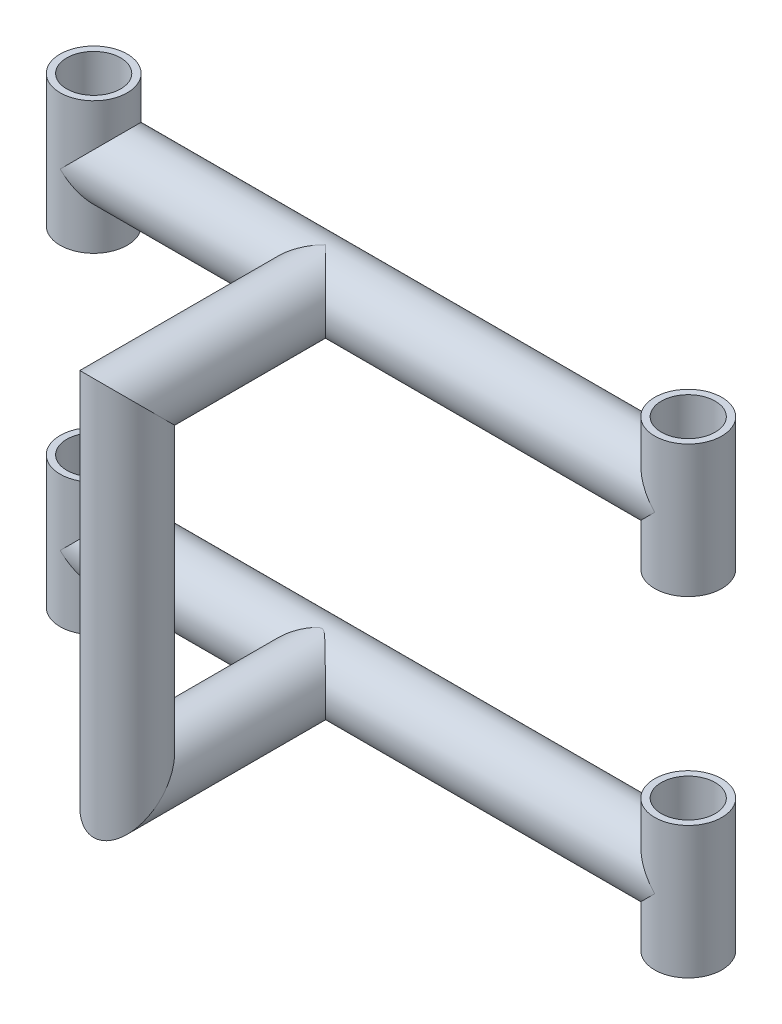
SolidWorks part; units mm, degrees
ref_plane "Alzado" through (0, 0, 0) normal (0, 0, 1) x (1, 0, 0)
ref_plane "Planta" through (0, 0, 0) normal (0, 1, 0) x (1, 0, 0)
ref_plane "Vista lateral" through (0, 0, 0) normal (1, 0, 0) x (0, 0, -1)
sketch "Croquis1" plane through (0, 0, 0) normal (0, 1, 0) x (1, 0, 0)
  circle A0 centre (0, 0) radius 25.4
  circle A1 centre (0, 0) radius 20.4
  dimension "D1" = 50.8
  dimension "D2" = 5
extrude "Saliente-Extruir1" add sketch "Croquis1" along normal blind 100
ref_plane "Plano3" through (0, 0, 0) normal (1, 0, 0) x (0, 0, -1)
sketch "Croquis7" plane through (0, 0, 0) normal (1, 0, 0) x (0, 0, -1)
  line L0 (-25.4, 100) -> (-25.4, 0) construction
  line L1 (-25.4, 0) -> (25.4, 0) construction
  line L2 (25.4, 0) -> (25.4, 100) construction
  line L3 (-25.4, 100) -> (25.4, 100) construction
  line L4 (0, 100) -> (0, 0) construction
  line L5 (-25.4, 50) -> (25.4, 50) construction
  circle A0 centre (0, 50) radius 25.4
  circle A1 centre (0, 50) radius 23.4
  dimension "D1" = 50.8
extrude "Saliente-Extruir2" add sketch "Croquis7" along normal blind 450
ref_plane "Plano4" through (225, 0, 0) normal (1, 0, 0) x (0, 0, -1)
mirror "Simetría1" about plane through (225, 0, 0) normal (1, 0, 0) of "Saliente-Extruir1"
ref_plane "Plano6" through (0, -200, 0) normal (0, 1, 0) x (1, 0, 0)
sketch "Croquis8" plane through (0, -200, 0) normal (0, 1, 0) x (1, 0, 0)
  circle A0 centre (0, 0) radius 25.4 construction
  arc A1 (0, -25.4) -> (0, 25.4) centre (0, 0) ccw construction
  circle A2 centre (0, 0) radius 20.4 construction
  circle A3 centre (450, 0) radius 20.4 construction
  circle A4 centre (450, 0) radius 25.4 construction
  circle A5 centre (0, 0) radius 25.4
  arc A6 (0, -25.4) -> (0, 25.4) centre (0, 0) ccw
  circle A7 centre (0, 0) radius 20.4
  circle A8 centre (450, 0) radius 20.4
  circle A9 centre (450, 0) radius 25.4
extrude "Saliente-Extruir3" add sketch "Croquis8" along normal mid plane 100 separate body contours A9 A8 | A5 A7 region at (17.4525, -200, 17.4525) region at (425.3184, -200, 0)
sketch "Croquis9" plane through (0, 0, 0) normal (1, 0, 0) x (0, 0, -1)
  line L0 (-25.4, -250) -> (25.4, -250) construction
  line L1 (25.4, -250) -> (25.4, -150) construction
  line L2 (-25.4, -150) -> (-25.4, -250) construction
  line L3 (25.4, -150) -> (-25.4, -150) construction
  line L4 (-25.4, -250) -> (25.4, -250) construction
  line L5 (25.4, -250) -> (25.4, -150) construction
  line L6 (-25.4, -150) -> (-25.4, -250) construction
  line L7 (25.4, -150) -> (-25.4, -150) construction
  line L8 (110.44, -200) -> (-110.44, -200) construction
  circle A0 centre (0, -200) radius 25.4
  circle A1 centre (0, -200) radius 23.4
  dimension "D1" = 50.8
extrude "Saliente-Extruir4" add sketch "Croquis9" along normal blind 450
sketch "Croquis10" plane through (0, 0, 0) normal (0, 0, 1) x (1, 0, 0)
  line L0 (-25.4, -200) -> (475.4, -200) construction
  line L1 (-25.4, -150) -> (-25.4, -250) construction
  line L2 (110.44, -200) -> (-110.44, -200) construction
  line L3 (225, -225.4) -> (225, -174.8928) construction
  line L4 (225, -27.94) -> (225, 27.94) construction
  line L5 (175.4, 75.4) -> (175.4, 24.6) construction
  line L7 (-25.4, 50) -> (475.4, 50) construction
  line L8 (-25.4, 100) -> (-25.4, 0) construction
  line L9 (475.4, 0) -> (475.4, 100) construction
  circle A1 centre (175.4, 50) radius 25.4
  point P12 (0, 0)
  point P13 (175.4, 61.4722)
  point P14 (0, 0)
  dimension "D2" = 50.8
  dimension "D1" = 300
sketch "Croquis14" plane through (225, 0, 0) normal (1, 0, 0) x (0, 0, -1)
  line L0 (0, 50) -> (-150, 50)
  line L1 (0, 75.4) -> (0, 24.6) construction
  line L2 (0, -200.1464) -> (-150, -200.1464)
  line L5 (0, -225.4) -> (0, -174.8928) construction
  line L7 (-150, -200.1464) -> (-150, 50)
  dimension "D1" = 150
sweep "Barrer3" add profiles "Croquis10" path "Croquis14"
sketch "Croquis15" plane through (0, -200, 0) normal (0, 1, 0) x (1, 0, 0)
  circle A0 centre (0, 0) radius 20.4 construction
  circle A1 centre (0, 0) radius 20.4
  circle A2 centre (450, 0) radius 20.4 construction
  circle A3 centre (450, 0) radius 20.4
extrude "Cortar-Extruir1" cut sketch "Croquis15" along normal through all
extrude "Cortar-Extruir2" cut sketch "Croquis15<2>" against normal through all
sketch "Croquis15<2>" plane through (0, -200, 0) normal (0, 1, 0) x (1, 0, 0) same geometry as "Croquis15"
equation "\"DiamExt\"=50.8"
equation "\"D1@Croquis1\"=\"DiamExt\""
equation "\"D2@Croquis1\"=\"DiamExt\"/10-0.08"
equation "\"Extrsuion\"= 100"
equation "\"D1@Saliente-Extruir1\"=\"Extrsuion\""
equation "\"D1@Croquis7\"=\"DiamExt\""
equation "\"L1\"=450"
equation "\"D1@Saliente-Extruir2\"=\"L1\""
equation "\"Esp\"=2"
equation "\"D2@Croquis7\"=\"Esp\""
equation "\"D1@Croquis9\"=\"DiamExt\""
equation "\"D2@Croquis9\"=\"Esp\""
equation "\"D1@Saliente-Extruir4\"=\"L1\""
equation "\"D1@Croquis14\"=\"L1\"/3"
equation "\"Dist2\"=300"
equation "\"D1@Croquis10\"=\"Dist2\""
